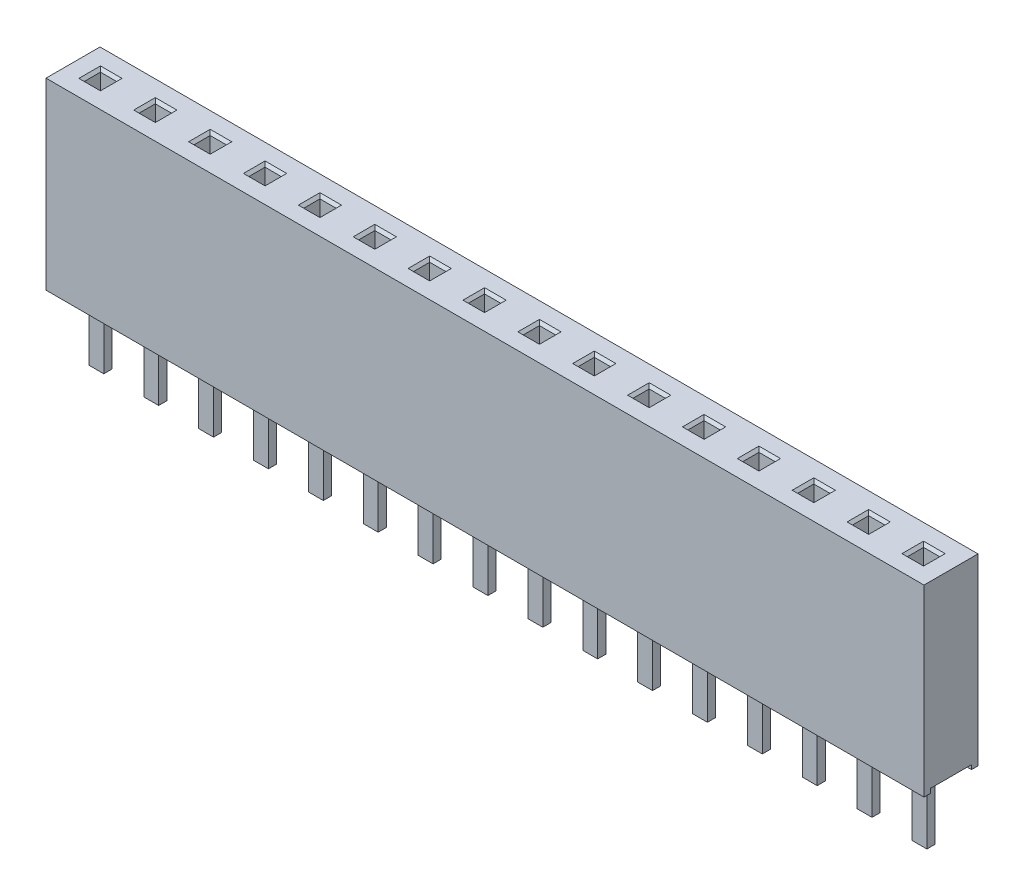
SolidWorks part; units mm, degrees
ref_plane "Front Plane" through (0, 0, 0) normal (0, 0, 1) x (1, 0, 0)
ref_plane "Top Plane" through (0, 0, 0) normal (0, 1, 0) x (1, 0, 0)
ref_plane "Right Plane" through (0, 0, 0) normal (1, 0, 0) x (0, 0, -1)
ref_axis "Axis1" through (0, 0, -88.99) along (0, 0, 1)
ref_axis "Axis2" through (0, -55, 0) along (0, 1, 0)
ref_axis "Axis3" through (-88.99, 0, 0) along (1, 0, 0)
sketch "Sketch1" plane through (0, 0, 0) normal (0, 1, 0) x (1, 0, 0)
  line L0 (0, 1.25) -> (0, -1.25) construction
  line L1 (39.37, -1.25) -> (-1.27, -1.25)
  line L2 (39.37, -1.25) -> (39.37, 1.25)
  line L3 (39.37, 1.25) -> (-1.27, 1.25)
  line L4 (-1.27, -1.25) -> (-1.27, 1.25)
  line L5 (38.1, 1.25) -> (38.1, -1.25) construction
  line L6 (0, 0) -> (-1.27, 0) construction
  line L7 (38.1, 0) -> (39.37, 0) construction
  line L8 (0, 0) -> (16, 0) construction
  point P0 (0, 0)
  dimension "D1" = 2.5
  dimension "D2" = 1.27
  dimension "D3" = 16
  dimension "pitchLength" = 38.1
extrude "Boss-Extrude1" add sketch "Sketch1" along normal blind 8.5
sketch "Sketch4" plane through (-1.27, 0, 0) normal (-1, 0, 0) x (0, 0, 1)
  line L0 (-1.25, 0) -> (1.25, 0) construction
  line L1 (-0.95, 0) -> (0.95, 0)
  line L2 (-0.95, 0) -> (-0.95, 0.2)
  line L3 (-0.95, 0.2) -> (0.95, 0.2)
  line L4 (0.95, 0) -> (0.95, 0.2)
  line L5 (-1.25, 8.5) -> (-1.25, 0) construction
  point P6 (0, 0)
  dimension "D1" = 0.3
  dimension "D2" = 0.2
extrude "Cut-Extrude2" cut sketch "Sketch4" against normal through all
sketch "Sketch2" plane through (0, 0.2, 0) normal (0, -1, 0) x (1, 0, 0)
  line L1 (0.345, -0.19) -> (-0.345, -0.19)
  line L2 (0.345, -0.19) -> (0.345, 0.19)
  line L3 (0.345, 0.19) -> (-0.345, 0.19)
  line L4 (-0.345, -0.19) -> (-0.345, 0.19)
  line L5 (0.345, -0.19) -> (-0.345, 0.19) construction
  line L6 (0.345, 0.19) -> (-0.345, -0.19) construction
  point P0 (0, 0)
  dimension "D1" = 0.69
  dimension "D2" = 0.38
extrude "Boss-Extrude2" add sketch "Sketch2" along normal offset from surface (3.4 mm away) 3.2 contours L4 L1 L2 L3 region at (0, 0.2, 0) up to face at (19.05, 0, 1.1) offset beyond the face yes
sketch "Sketch3" plane through (0, 8.5, 0) normal (0, 1, 0) x (1, 0, 0)
  line L1 (0.375, -0.375) -> (-0.375, -0.375)
  line L2 (0.375, -0.375) -> (0.375, 0.375)
  line L3 (0.375, 0.375) -> (-0.375, 0.375)
  line L4 (-0.375, -0.375) -> (-0.375, 0.375)
  line L5 (0.375, -0.375) -> (-0.375, 0.375) construction
  line L6 (0.375, 0.375) -> (-0.375, -0.375) construction
  point P0 (0, 0)
  dimension "D1" = 0.75
extrude "Cut-Extrude1" cut sketch "Sketch3" against normal blind 6.05
chamfer "Chamfer1" distance 0.125 angle 45 4 edges at (0, 8.5, 0.375) (0.375, 8.5, 0) (0, 8.5, -0.375) (-0.375, 8.5, 0)
chamfer "Chamfer2" distance 0.125 angle 45 4 edges at (0, -3.2, -0.19) (-0.345, -3.2, 0) (0.345, -3.2, 0) (0, -3.2, 0.19)
pattern_linear "LPattern1" count 16 spacing 2.54 along (1, 0, 0) of "Cut-Extrude1", "Chamfer1", "Boss-Extrude2", "Chamfer2"
mirror "Mirror1" [suppressed] of bodies 109
equation "\"pitch\"= 2.54"
equation "\"pitchLength@Sketch1\"=\"pitch\" * (\"pos\" - 1)"
equation "\"D3@LPattern1\"=\"pitch\""
equation "\"D1@LPattern1\"  = \"pos\""
equation "\"pos\"= \"D3@Sketch1\""
